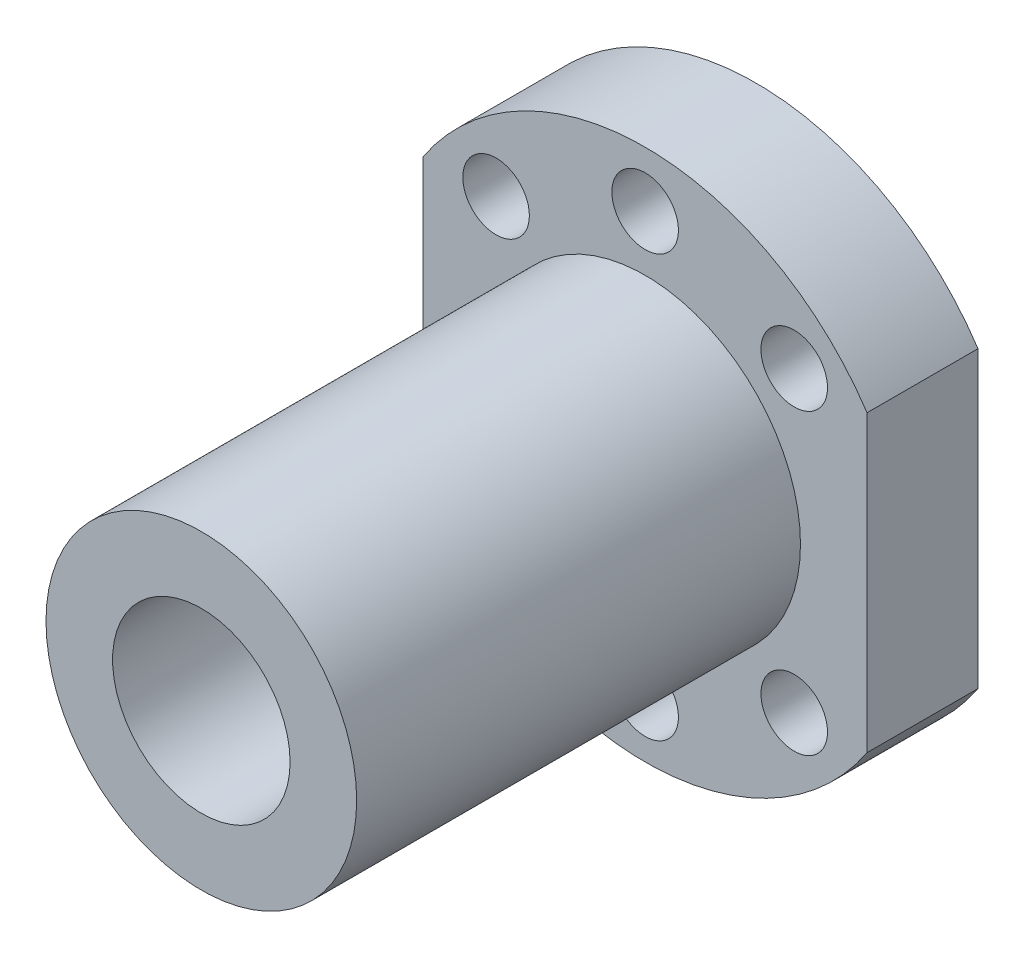
SolidWorks part; units mm, degrees
note: The reader was unsure of these and kept them because the rebuilt part matched: shared geometry of "Sketch1<5>".
material "7079 Alloy"
ref_plane "Front" through (0, 0, 0) normal (0, 0, 1) x (1, 0, 0)
ref_plane "Top" through (0, 0, 0) normal (0, 1, 0) x (1, 0, 0)
ref_plane "Right" through (0, 0, 0) normal (1, 0, 0) x (0, 0, -1)
sketch "Sketch1" plane through (0, 0, 0) normal (0, 0, 1) x (1, 0, 0)
  line L0 (0, 0) -> (0, 19)
  line L1 (0, 0) -> (13.435, 13.435)
  line L2 (0, 0) -> (-13.435, 13.435)
  line L3 (0, 0) -> (0, -19)
  line L4 (0, 0) -> (13.435, -13.435)
  line L5 (0, 0) -> (-13.435, -13.435)
  line L6 (0, 0) -> (20, 0)
  line L7 (0, 0) -> (-20, 0)
  line L8 (-20, 0) -> (-20, 13.2665)
  line L9 (-20, 13.2665) -> (-20, -13.2665)
  line L10 (20, 0) -> (20, 13.2665)
  line L11 (20, 13.2665) -> (20, -13.2665)
  circle A0 centre (0, 0) radius 8
  circle A1 centre (0, 0) radius 14
  arc A2 (-20, -13.2665) -> (20, -13.2665) centre (0, 0) ccw
  circle A3 centre (-13.435, 13.435) radius 3
  circle A4 centre (0, 19) radius 3
  circle A5 centre (13.435, 13.435) radius 3
  circle A6 centre (13.435, -13.435) radius 3
  circle A7 centre (0, -19) radius 3
  circle A8 centre (-13.435, -13.435) radius 3
  arc A10 (20, 13.2665) -> (-20, 13.2665) centre (0, 0) ccw
  dimension "D1" = 20
extrude "Extrude4" add sketch "Sketch1" along normal blind 10
extrude "Extrude5" add sketch "Sketch1<5>" along normal blind 50 contours L1 A1 L0 A0 | L0 A1 L2 A0 | L6 A1 L1 A0 | L4 A1 L6 A0 | L3 A1 L4 A0 | L5 A1 L3 A0 | L7 A1 L5 A0 | L2 A1 L7 A0
sketch "Sketch1<5>" plane through (0, 0, 0) normal (0, 0, 1) x (1, 0, 0) same geometry as "Sketch1"
